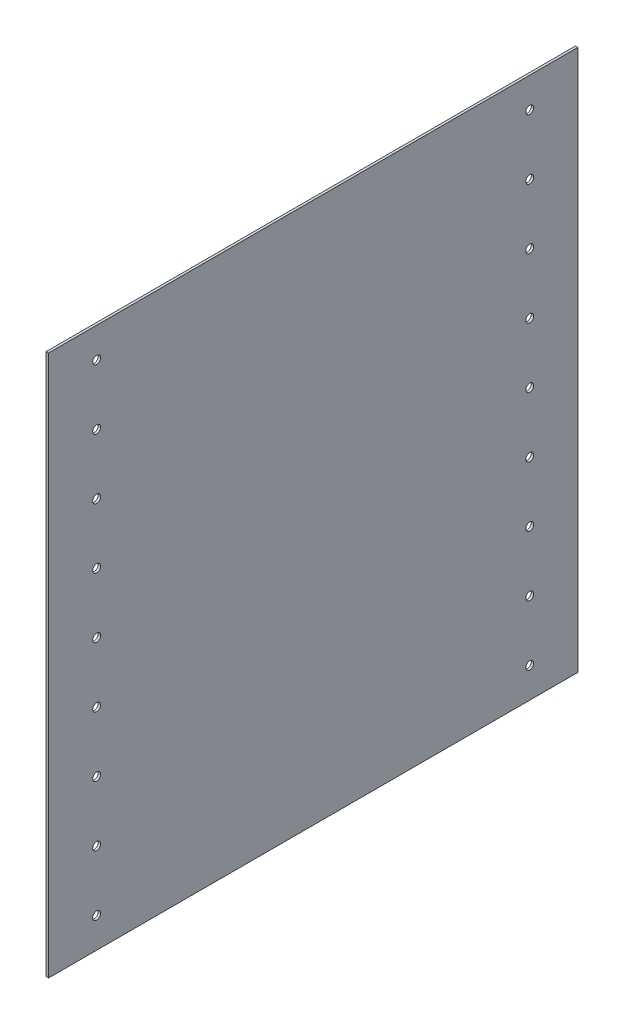
SolidWorks part; units mm, degrees
material "Простая углеродистая сталь"
ref_plane "Спереди" through (0, 0, 0) normal (0, 0, 1) x (1, 0, 0)
ref_plane "Сверху" through (0, 0, 0) normal (0, 1, 0) x (1, 0, 0)
ref_plane "Справа" through (0, 0, 0) normal (1, 0, 0) x (0, 0, -1)
sketch "Эскиз1" plane through (0, 0, 0) normal (0, 0, 1) x (1, 0, 0)
  line L0 (0, 0) -> (0, 450)
  dimension "D1" = 450
sheet metal parameters "Листовой металл1" thickness 2 parameters "D1"=1.8, "Толщина"=2
base flange "Базовая кромка1" sketch "Эскиз1" end condition blind depth 440 reverse direction no thickness 2 reverse thickness direction no bend radius 1.8
hole_wizard "Отверстие с зазором M61" positions "Эскиз3" profile "Эскиз2" hole size "M6" standard "DIN"
sketch "Эскиз3" plane through (2, 0, 0) normal (1, 0, 0) x (0, 0, -1)
  line L0 (-440, 0) -> (-440, 450) construction
  line L1 (-440, 450) -> (0, 450) construction
  line L2 (-220, 450) -> (-220, 275) construction
  point P0 (-400, 425)
  point P12 (-400, 375)
  point P13 (-400, 325)
  point P14 (-400, 275)
  point P15 (-400, 225)
  point P16 (-400, 175)
  point P17 (-400, 125)
  point P18 (-400, 75)
  point P19 (-400, 25)
  point P24 (-40, 25)
  point P25 (-40, 75)
  point P26 (-40, 125)
  point P27 (-40, 175)
  point P28 (-40, 225)
  point P29 (-40, 275)
  point P30 (-40, 325)
  point P31 (-40, 375)
  point P32 (-40, 425)
  dimension "D1" = 40
  dimension "D2" = 25
  dimension "D3" = 9
sketch "Эскиз2" plane through (2, 425, 400) normal (0, 1, 0) x (0, 0, -1)
  line L0 (0, 0) -> (0, 6.9828)
  line L1 (0, 6.9828) -> (3.3, 5)
  line L2 (3.3, 5) -> (3.3, 0)
  line L5 (3.3, 0) -> (0, 0)
  line L10 (0, 6.9828) -> (-3.3, 5) construction
  line L11 (0, -6.35) -> (0, 107.95) construction
  dimension "Диаметр отверстия" = 6.6
  dimension "Глубина отверстия" = 5
  dimension "Угол заточки сверла" = 118
flat pattern "Развертка1" [suppressed]
sketch "Сгиб-Линии1" plane through (0, 0, 0) normal (0, 1, 0) x (-1, 0, 0)
sketch3d "Граничная рамка1" [suppressed]
  line L0 (0, 500, 0) -> (0, 0, 0) construction
  line L1 (-440, 500, 0) -> (-440, 0, 0) construction
  line L2 (0, 500, 0) -> (-440, 500, 0) construction
  line L3 (0, 0, 0) -> (-440, 0, 0) construction
